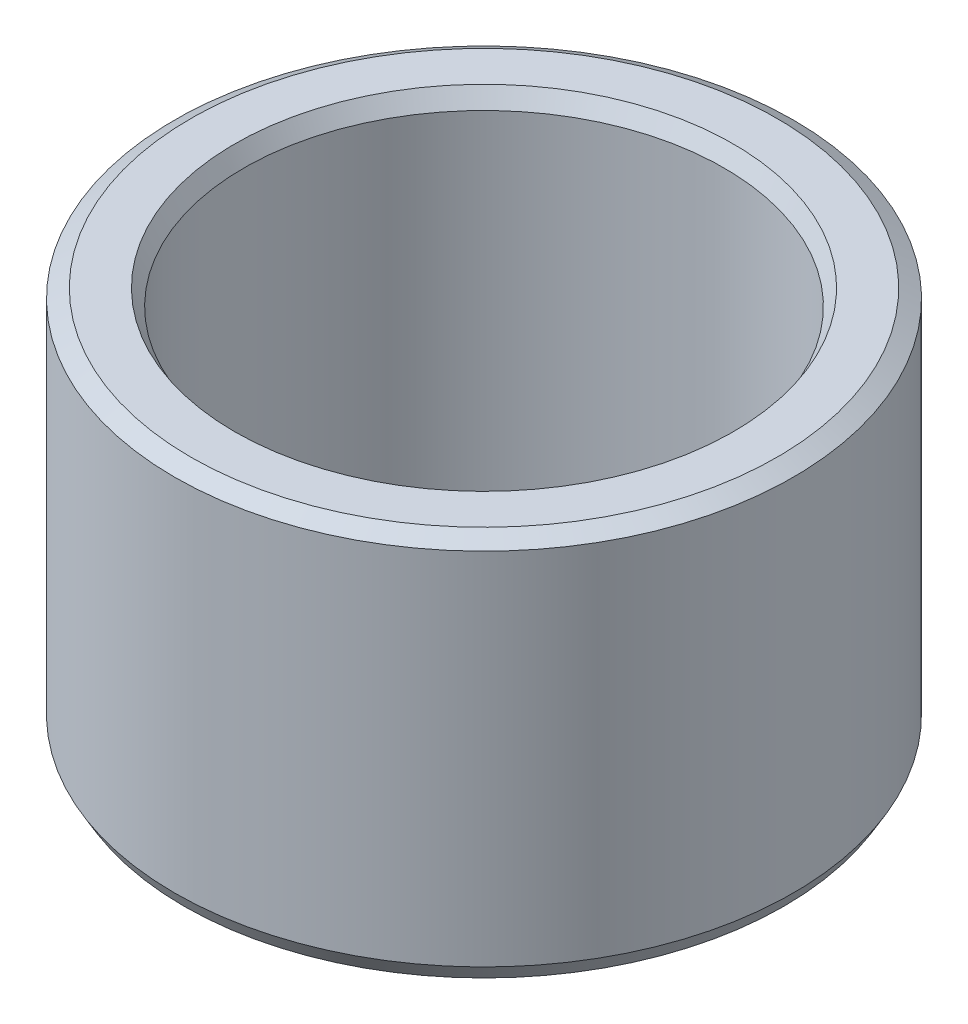
SolidWorks part; units mm, degrees
ref_plane "Front Plane" through (0, 0, 0) normal (0, 0, 1) x (1, 0, 0)
ref_plane "Top Plane" through (0, 0, 0) normal (0, 1, 0) x (1, 0, 0)
ref_plane "Right Plane" through (0, 0, 0) normal (1, 0, 0) x (0, 0, -1)
sketch "Sketch1" plane through (0, 0, 0) normal (0, 1, 0) x (1, 0, 0)
  circle A0 centre (0, 0) radius 35
  dimension "SLEEVE_OD" = 70
extrude "Boss-Extrude1" add sketch "Sketch1" along normal blind 43.6124
sketch "Sketch2" plane through (0, 0, 0) normal (0, 1, 0) x (1, 0, 0)
  circle A0 centre (0, 0) radius 27.1518
  dimension "BORE_D" = 54.3036
extrude "Cut-Extrude1" cut sketch "Sketch2" along normal through all
chamfer "Chamfer1" distance 1.0532 angle 60 4 edges at (0, 43.6124, 27.1518) (0, 0, 27.1518) (0, 0, 35) (0, 43.6124, 35) first distance on face at (0, 43.6124, 27.1518) first distance on face at (0, 0, 27.1518) first distance on face at (0, 43.6124, 35)
